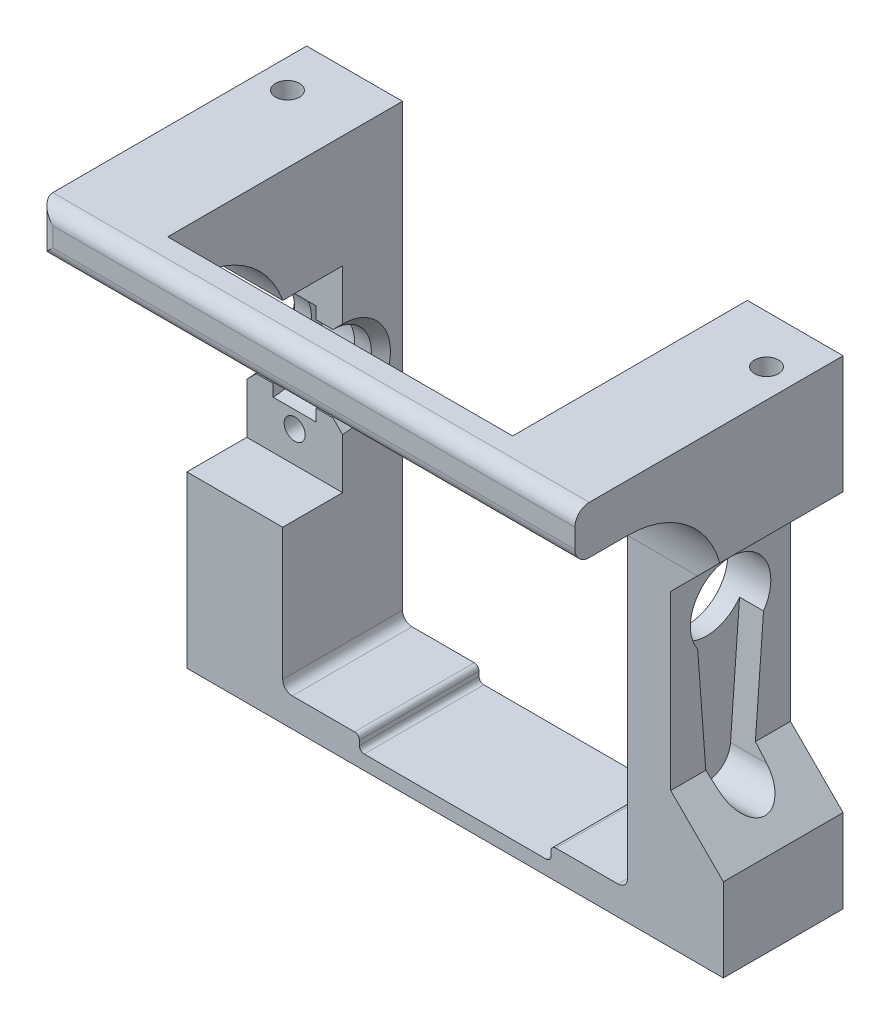
SolidWorks part; units mm, degrees
ref_plane "Спереди" through (0, 0, 0) normal (0, 0, 1) x (1, 0, 0)
ref_plane "Сверху" through (0, 0, 0) normal (0, 1, 0) x (1, 0, 0)
ref_plane "Справа" through (0, 0, 0) normal (1, 0, 0) x (0, 0, -1)
sketch "Эскиз1" plane through (0, 0, 0) normal (0, 0, 1) x (1, 0, 0)
  line L1 (-28, -25) -> (28, -25)
  line L2 (-28, -25) -> (-28, 25)
  line L3 (-28, 25) -> (28, 25)
  line L4 (28, -25) -> (28, 25)
  line L5 (-28, -25) -> (28, 25) construction
  line L6 (-28, 25) -> (28, -25) construction
  point P0 (0, 0)
  dimension "D1" = 56
  dimension "D2" = 50
extrude "тело" add sketch "Эскиз1" along normal blind 12.5
sketch "Эскиз3" plane through (0, 0, 12.5) normal (0, 0, 1) x (1, 0, 0)
  line L1 (-18, -22) -> (18, -22)
  line L2 (-18, -22) -> (-18, 24)
  line L3 (-18, 24) -> (18, 24)
  line L4 (18, -22) -> (18, 24)
  line L5 (-28, -25) -> (28, -25) construction
  point P0 (0, 1)
  point P6 (0, -22)
  point P9 (-18, 1)
  point P10 (0, -25)
  dimension "D1" = 36
  dimension "D2" = 46
  dimension "D3" = 3
extrude "отверстие под серво" cut sketch "Эскиз3" against normal through all
sketch "Эскиз11" plane through (0, -25, 0) normal (0, -1, 0) x (1, 0, 0)
  line L0 (0, 12.5) -> (0, 0) construction
  line L1 (-28, 12.5) -> (28, 12.5) construction
  line L2 (-25, 5) -> (25, 5) construction
  line L3 (-28, 0) -> (28, 0) construction
  circle A0 centre (-25, 5) radius 1.25
  circle A1 centre (25, 5) radius 1.25
  point P8 (0, 5)
  dimension "D1" = 2.5
  dimension "D2" = 50
  dimension "D3" = 5
extrude "Крепежные отверстия сверху" cut sketch "Эскиз11" against normal blind 10
mirror "Крепежные отверстия снизу" about plane through (0, 0, 0) normal (0, 1, 0) of "Крепежные отверстия сверху"
sketch "Эскиз5" plane through (28, 0, 0) normal (1, 0, 0) x (0, 0, -1)
  line L0 (-9.2, 0.7667) -> (-8.2445, -12.0487) construction
  line L1 (-6.25, 3) -> (-6.25, -13.9) construction
  line L2 (-6.25, 6.7) -> (-6.25, -13.9) construction
  line L3 (-9.2, 0.7667) -> (-6.25, 0.7667) construction
  line L4 (-6.25, 0.7667) -> (-6.25, -13.9) construction
  line L5 (-3.3, 0.7667) -> (-4.2555, -12.0487) construction
  line L6 (-9.688, 0.5875) -> (-8.7431, -12.0859)
  line L7 (-2.812, 0.5875) -> (-3.7569, -12.0859)
  line L8 (-12.5, -25) -> (0, -25) construction
  arc A0 (-2.812, 0.5875) -> (-9.688, 0.5875) centre (-6.25, 3) ccw
  arc A1 (-8.2445, -12.0487) -> (-4.2555, -12.0487) centre (-6.25, -11.9) ccw construction
  arc A2 (-8.7431, -12.0859) -> (-3.7569, -12.0859) centre (-6.25, -11.9) ccw
  arc A3 (-3.3, 0.7667) -> (-9.2, 0.7667) centre (-6.25, 3) ccw construction
  dimension "D1" = 2.95
  dimension "D2" = 4
  dimension "D4" = 7.4
  dimension "D5" = 0.5
  dimension "D3" = 20.6
  dimension "D6" = 28
extrude "вырез под качалку" cut sketch "Эскиз5" against normal offset from surface (8 mm away) 2 up to face at (18, 1, 6.25)
sketch "Эскиз4" plane through (28, 0, 0) normal (1, 0, 0) x (0, 0, -1)
  line L0 (-6.25, 25) -> (-6.25, -25) construction
  line L1 (-12.5, 25) -> (0, 25) construction
  line L2 (-12.5, -25) -> (0, -25) construction
  line L4 (-12.5, -25) -> (-12.5, 25) construction
  line L5 (-12.5, 0) -> (0, 0) construction
  line L6 (0, -25) -> (0, 25) construction
  circle A0 centre (-6.25, 3) radius 4.2
  arc A2 (-2.812, 0.5875) -> (-9.688, 0.5875) centre (-6.25, 3) ccw construction
extrude "вырез под ось вращения" cut sketch "Эскиз4" against normal up to next
sketch "Эскиз6" plane through (-28, 0, 0) normal (-1, 0, 0) x (0, 0, 1)
  circle A0 centre (6.25, 3) radius 4
  dimension "D1" = 8
extrude "вырез под ось подшипника" cut sketch "Эскиз6" against normal up to surface (10 mm away) up to face at (-18, 1, 6.25)
sketch "Эскиз7" plane through (-28, 0, 0) normal (-1, 0, 0) x (0, 0, 1)
  line L0 (12.5, 25) -> (12.5, -25) construction
  line L1 (6.25, 13.25) -> (12.5, 13.25)
  line L2 (6.25, 13.25) -> (6.25, -7.25)
  line L3 (6.25, -7.25) -> (12.5, -7.25)
  line L4 (12.5, 13.25) -> (12.5, -7.25)
  point P6 (6.25, 3)
  point P7 (6.25, 3)
  dimension "D1" = 20.5
extrude "вырез под крепление подшипника" cut sketch "Эскиз7" against normal up to surface (10 mm away) up to face at (-18, 3, 10.25)
ref_plane "Плоскость1" through (-23, 0, 0) normal (-1, 0, 0) x (0, 0, 1)
sketch "Эскиз8" plane through (-23, 0, 0) normal (-1, 0, 0) x (0, 0, 1)
  circle A0 centre (6.25, 3) radius 5.25
  dimension "D1" = 10.5
extrude "вырез под подшипник" cut sketch "Эскиз8" against normal mid plane 4.5
sketch "Эскиз9" plane through (0, 0, 6.25) normal (0, 0, 1) x (1, 0, 0)
  line L1 (-28, 3) -> (-18, 3) construction
  line L3 (-28, 7) -> (-28, -1) construction
  line L4 (-18, -1) -> (-18, 7) construction
  line L5 (-23, -4) -> (-23, 10) construction
  circle A0 centre (-23, 10) radius 1.1
  circle A1 centre (-23, -4) radius 1.1
  point P9 (-23, 3)
  dimension "D1" = 2.2
  dimension "D2" = 14
extrude "отверстия под саморезы" cut sketch "Эскиз9" against normal offset from surface (5.25 mm away) 1 up to face at (0, 1, 0)
sketch "Эскиз10" plane through (0, 0, 12.5) normal (0, 0, 1) x (1, 0, 0)
  line L1 (28, -25) -> (28, 25) construction
  line L2 (18, -22) -> (18, 24) construction
  line L3 (28, -16.3) -> (28, 12.7)
  line L4 (22.5, -10.8) -> (22.5, 7.2)
  line L5 (28, 12.7) -> (22.5, 7.2)
  line L6 (22.5, -10.8) -> (28, -16.3)
  line L8 (28, 7.2) -> (18, 7.2) construction
  dimension "D1" = 45
  dimension "D2" = 4.5
  dimension "D3" = 18
  dimension "D4" = 45
extrude "вырез чтобы вставлять качалку" cut sketch "Эскиз10" against normal through all
chamfer "Фаска1" distance 1 angle 45 2 edges at (-28, 3, 2.25) (-18, 3, 2.25)
fillet "Скругление1" radius 1 2 edges at (18, -22, 6.25) (-18, -22, 6.25)
sketch "Эскиз12" plane through (0, 0, 0) normal (0, 0, 1) x (1, 0, 0)
  line L0 (-17, -22) -> (17, -22) construction
  line L1 (-10, -22) -> (10, -22)
  line L2 (-10, -22) -> (-10, -23.5)
  line L3 (-10, -23.5) -> (10, -23.5)
  line L4 (10, -22) -> (10, -23.5)
  point P6 (0, -22)
  dimension "D1" = 20
  dimension "D2" = 1.5
extrude "вырез под шлейф" cut sketch "Эскиз12" along normal through all
fillet "Скругление2" radius 0.5 4 edges at (10, -23.5, 6.25) (10, -22, 6.25) (-10, -23.5, 6.25) (-10, -22, 6.25)
sketch "Эскиз13" plane through (0, 0, 12.5) normal (0, 0, 1) x (1, 0, 0)
  line L1 (-18, 24) -> (18, 24)
  line L2 (-18, 24) -> (-18, 25)
  line L3 (-18, 25) -> (18, 25)
  line L4 (18, 24) -> (18, 25)
  line L5 (28, 25) -> (-28, 25) construction
extrude "Удаление нижней перекладины" cut sketch "Эскиз13" against normal up to next
sketch "Эскиз14" plane through (0, 25, 0) normal (0, 1, 0) x (1, 0, 0)
  line L0 (-28, -12.5) -> (-28, -28)
  line L1 (0, 0) -> (0, -28) construction
  line L2 (-28, -12.5) -> (-18, -12.5)
  line L3 (-18, -12.5) -> (-18, -24.5)
  line L4 (-18, -24.5) -> (18, -24.5)
  line L5 (-28, -28) -> (28, -28)
  line L6 (18, -12.5) -> (18, -24.5)
  line L7 (28, -12.5) -> (18, -12.5)
  line L8 (28, -12.5) -> (28, -28)
  point P13 (0, -24.5)
  dimension "D1" = 15.5
  dimension "D2" = 12
extrude "Нижняя скоба жесткости" add sketch "Эскиз14" against normal blind 5
fillet "Скругление3" radius 10 2 edges at (23, 20, 12.5) (-23, 20, 12.5)
fillet "Скругление4" radius 1.5 4 edges at (0, 20, 28) (0, 25, 28) (-28, 22.5, 28) (0, 20, 24.5)
sketch "Эскиз15" plane through (0, 0, 0) normal (0, 0, -1) x (-1, 0, 0)
  line L0 (0, 25) -> (0, 0) construction
  line L1 (-18, 25) -> (18, 25) construction
  line L2 (-28, 25) -> (-18, 25) construction
  line L4 (-26.4, 11.1) -> (-28, 12.7)
  line L5 (-34, 25) -> (-28, 25)
  line L6 (-28, 12.7) -> (-28, 25) construction
  line L7 (-28, 12.7) -> (-22.5, 7.2) construction
  line L8 (-28, 12.7) -> (-28, 25)
  line L9 (-34, 18.05) -> (-28, 18.05) construction
  line L10 (-34, 11.1) -> (-26.4, 11.1)
  line L11 (34, 11.1) -> (28, 11.1)
  line L12 (34, 25) -> (28, 25)
  line L13 (28, 25) -> (28, -25) construction
  line L14 (28, 25) -> (28, 11.1)
  arc A0 (-36.5156, 13.2153) -> (-36.5156, 22.8847) centre (-34, 18.05) ccw
  arc A1 (-34, 25) -> (-37.208, 24.2153) centre (-34, 18.05) ccw
  arc A2 (-37.208, 24.2153) -> (-36.5156, 22.8847) centre (-36.8618, 23.55) ccw
  arc A4 (-37.208, 11.8847) -> (-36.5156, 13.2153) centre (-36.8618, 12.55) cw
  arc A5 (-37.208, 11.8847) -> (-34, 11.1) centre (-34, 18.05) ccw
  arc A6 (37.208, 11.8847) -> (34, 11.1) centre (34, 18.05) cw
  arc A7 (37.208, 11.8847) -> (36.5156, 13.2153) centre (36.8618, 12.55) ccw
  arc A8 (34, 25) -> (37.208, 24.2153) centre (34, 18.05) cw
  arc A9 (37.208, 24.2153) -> (36.5156, 22.8847) centre (36.8618, 23.55) cw
  arc A10 (36.5156, 13.2153) -> (36.5156, 22.8847) centre (34, 18.05) cw
  dimension "D1" = 10.9
  dimension "D2" = 1.5
  dimension "D3" = 34
  dimension "D4" = 11
extrude "Крепление фар" [suppressed] add sketch "Эскиз15" against normal blind 12.5
fillet "Скругление5" [suppressed] radius 1
